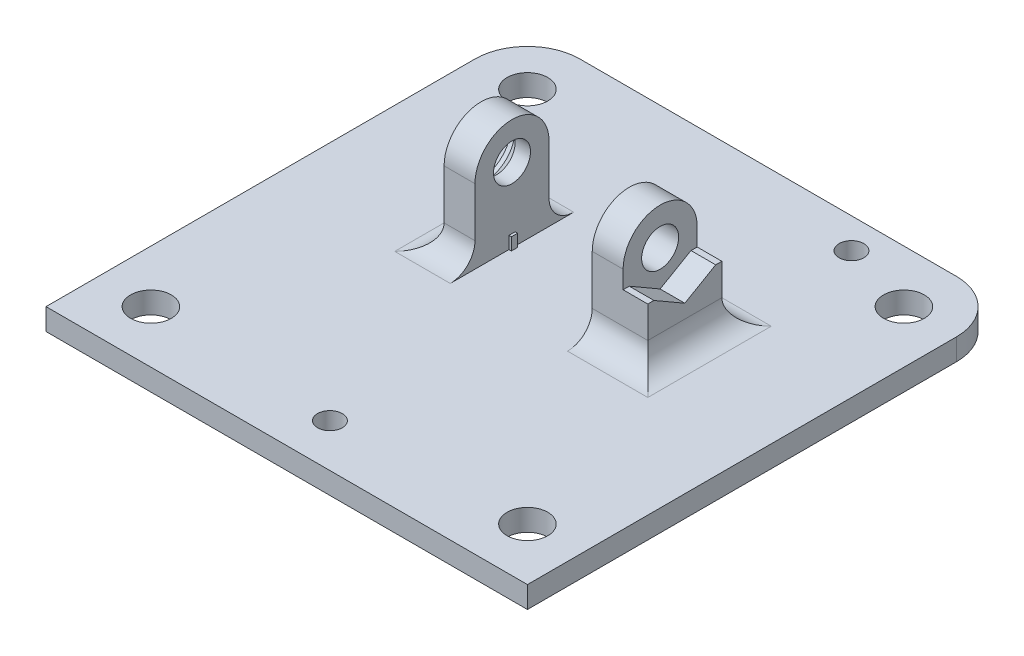
SolidWorks part; units mm, degrees
ref_plane "Front Plane" through (0, 0, 0) normal (0, 0, 1) x (1, 0, 0)
ref_plane "Top Plane" through (0, 0, 0) normal (0, 1, 0) x (1, 0, 0)
ref_plane "Right Plane" through (0, 0, 0) normal (1, 0, 0) x (0, 0, -1)
sketch "Sketch1" plane through (0, 0, 0) normal (0, 1, 0) x (1, 0, 0)
  line L0 (-19.5, 35.2) -> (-19.5, -19.5) construction
  line L1 (-19.5, 19.5) -> (19.5, 19.5)
  line L2 (-19.5, 19.5) -> (-19.5, -19.5)
  line L3 (-19.5, -19.5) -> (19.5, -19.5)
  line L4 (19.5, 19.5) -> (19.5, -19.5)
  line L5 (-19.5, 19.5) -> (19.5, -19.5) construction
  line L6 (-19.5, -19.5) -> (19.5, 19.5) construction
  line L7 (-19.5, -19.5) -> (19.5, -19.5) construction
  line L8 (0, -19.5) -> (0, 19.5) construction
  circle A0 centre (-15.25, -15.25) radius 1.65 construction
  circle A1 centre (15.25, -15.25) radius 1.65 construction
  circle A2 centre (9.2, 17.05) radius 1 construction
  circle A3 centre (15.25, 15.25) radius 1.65 construction
  circle A4 centre (-15.25, 15.25) radius 1.65 construction
  circle A5 centre (-15.25, -15.25) radius 1.65
  circle A6 centre (15.25, -15.25) radius 1.65
  circle A7 centre (9.2, 17.05) radius 1
  circle A8 centre (15.25, 15.25) radius 1.65
  circle A9 centre (-15.25, 15.25) radius 1.65
  circle A10 centre (-15.25, 15.25) radius 4.25
  circle A11 centre (15.25, 15.25) radius 4.25
  circle A12 centre (-15.25, -15.25) radius 4.25
  circle A13 centre (15.25, -15.25) radius 4.25
  circle A14 centre (0, -16) radius 1
  point P0 (0, 0)
  dimension "D1" = 2
  dimension "D2" = 3.5
extrude "Shape" add sketch "Sketch1" along normal blind 1.75 contours A13 L4 A11 L1 A10 L2 A12 L3 A7 | A10 A9 | A11 A8 | A13 A6 | A12 A5 | A12 L2 L3 | A13 L3 L4 region at (-0.0227, 0, 0.0026) region at (-12.3298, 0, -18.1702) region at (18.1702, 0, -18.1702) region at (-18.5507, 0, 18.5507) region at (-15.25, 0, 11.1202) region at (18.1702, 0, 18.1702) region at (18.5507, 0, 18.5507)
sketch "Sketch3" plane through (0, 1.75, 0) normal (0, 1, 0) x (1, 0, 0)
  line L0 (0, 19.5) -> (0, -19.5) construction
  line L1 (-15.25, 19.5) -> (15.25, 19.5) construction
  line L2 (-19.5, -19.5) -> (19.5, -19.5) construction
  line L3 (-19.5, 3.5) -> (19.5, 3.5) construction
  line L4 (-19.5, 15.25) -> (-19.5, -19.5) construction
  line L5 (19.5, 15.25) -> (19.5, -19.5) construction
  line L6 (4.75, 6.5) -> (7.25, 6.5)
  line L7 (-4.75, 6.5) -> (-7.25, 6.5)
  line L8 (-4.75, 6.5) -> (-4.75, 0.5)
  line L9 (-4.75, 0.5) -> (-7.25, 0.5)
  line L10 (-7.25, 6.5) -> (-7.25, 0.5)
  line L11 (-4.75, 6.5) -> (-7.25, 0.5) construction
  line L12 (-4.75, 0.5) -> (-7.25, 6.5) construction
  line L13 (4.75, 6.5) -> (4.75, 0.5)
  line L14 (4.75, 0.5) -> (7.25, 0.5)
  line L15 (7.25, 6.5) -> (7.25, 0.5)
  line L17 (7.25, 6.5) -> (9.25, 6.5)
  line L18 (7.25, 6.5) -> (7.25, 0.5)
  line L19 (7.25, 0.5) -> (9.25, 0.5)
  line L20 (9.25, 6.5) -> (9.25, 0.5)
  point P12 (-6, 3.5)
  dimension "D1" = 16
  dimension "D2" = 9.5
  dimension "D3" = 2.5
  dimension "D4" = 6
  dimension "D5" = 4.5
extrude "Supports" add sketch "Sketch3" along normal blind 9 contours L7 L10 L9 L8 | L15 L6 L13 L14 | L20 L17 L15 L19 region at (6, 1.75, -3.5) region at (8.25, 1.75, -3.5) region at (-6, 1.75, -3.5)
sketch "Sketch4" plane through (-7.25, 0, 0) normal (-1, 0, 0) x (0, 0, 1)
  line L0 (-3.5, 10.75) -> (-3.5, 1.75) construction
  line L2 (-6.5, 1.75) -> (-0.5, 1.75) construction
  line L3 (-0.5, 10.75) -> (-0.5, 1.75) construction
  line L4 (-6.5, 10.75) -> (-0.5, 10.75) construction
  circle A0 centre (-3.5, 7.75) radius 3
  circle A1 centre (-3.5, 7.75) radius 1.5
  line M2 (-0.5, 1.75) -> (-0.5, 10.75)
  line M4 (-6.5, 10.75) -> (-6.5, 1.75)
  line M11 (-0.5, 10.75) -> (-6.5, 10.75)
  dimension "D1" = 3
extrude "Support cuts" cut sketch "Sketch4" against normal up to surface (16.5 mm away) contours A1 L0 | L0 A1 | A0 M11 M4 | A0 M2 M11 region at (-7.25, 10.0799, -1.1701) region at (-7.25, 10.0799, -5.8299) region at (-7.25, 7.75, -2.8634) region at (-7.25, 7.75, -4.1366) up to face at (9.25, 6.25, -3.5)
fillet "Fillet1" radius 2 6 edges at (-6, 1.75, -6.5) (7, 1.75, -6.5) (7, 1.75, -0.5) (-6, 1.75, -0.5) (-7.25, 1.75, -3.5) (9.25, 1.75, -3.5)
sketch "Sketch5" plane through (9.25, 0, 0) normal (1, 0, 0) x (0, 0, -1)
  line L0 (1, 6.3066) -> (0.5, 6.3066)
  line L1 (3.5, 4.8632) -> (6, 6.3066)
  line L2 (6, 6.3066) -> (6, 9.1934)
  line L3 (6, 9.1934) -> (3.5, 10.6368)
  line L4 (3.5, 10.6368) -> (1, 9.1934)
  line L5 (1, 9.1934) -> (1, 6.3066)
  line L6 (1, 6.3066) -> (3.5, 4.8632)
  line L7 (6, 6.3066) -> (6.5, 6.3066)
  line L9 (0.5, 7.75) -> (0.5, 3.75)
  line L10 (0.5, 3.75) -> (6.5, 3.75)
  line L11 (6.5, 3.75) -> (6.5, 7.75)
  line L12 (0.5, 7.75) -> (0.5, 3.75)
  line L13 (0.5, 3.75) -> (6.5, 3.75)
  line L14 (6.5, 3.75) -> (6.5, 7.75)
  circle A0 centre (3.5, 7.75) radius 2.5 construction
  circle A1 centre (3.5, 7.75) radius 1.5 construction
  arc A2 (6.5, 7.75) -> (0.5, 7.75) centre (3.5, 7.75) ccw
  arc A3 (6.5, 7.75) -> (0.5, 7.75) centre (3.5, 7.75) ccw
  circle M3 centre (3.5, 7.75) radius 1.5
  line M4 (0.5, 7.75) -> (0.5, 3.75)
  line M6 (6.5, 3.75) -> (6.5, 7.75)
  arc M7 (6.5, 7.75) -> (0.5, 7.75) centre (3.5, 7.75) ccw
  dimension "D1" = 5
  dimension "D2" = 0
extrude "Nut holder" cut sketch "Sketch5" against normal blind 2 contours L5 L6 L1 L2 L3 L4 M3 | L2 L7 L0 L5 L4 L3 M6 M7 M4 region at (9.25, 6.3813, -0.75) region at (9.25, 7.75, -1.0764)
sketch "Sketch6" plane through (-7.25, 0, 0) normal (-1, 0, 0) x (0, 0, 1)
  circle A0 centre (-3.5, 7.75) radius 2.4
  dimension "D1" = 4.8
extrude "Screw cut" cut sketch "Sketch6" against normal blind 0.35
chamfer "Scew chamfer" distance 0.9 angle 45 1 edges at (-6.9, 7.75, -2)
sketch "Sketch7" plane through (4.75, 0, 0) normal (-1, 0, 0) x (0, 0, 1)
  line L0 (-3.5, 1.75) -> (-3.5, 10.75) construction
  line L1 (-8.5, 1.75) -> (1.5, 1.75) construction
  line L3 (-3.25, 2.75) -> (-3.75, 2.75)
  line L4 (-3.25, 2.75) -> (-3.25, 1.75)
  line L5 (-3.25, 1.75) -> (-3.75, 1.75)
  line L6 (-3.75, 2.75) -> (-3.75, 1.75)
  line L7 (-3.25, 2.75) -> (-3.75, 1.75) construction
  line L8 (-3.25, 1.75) -> (-3.75, 2.75) construction
  arc A0 (-0.5, 7.75) -> (-6.5, 7.75) centre (-3.5, 7.75) ccw construction
  point P7 (-3.5, 2.25)
  dimension "D1" = 0.5
  dimension "D2" = 1
extrude "Angle fix 1" add sketch "Sketch7" along normal blind 0.2
sketch "Sketch8" plane through (-4.75, 0, 0) normal (1, 0, 0) x (0, 0, -1)
  line L4 (3.75, 1.75) -> (3.75, 2.75)
  line L5 (3.25, 1.75) -> (3.75, 1.75)
  line L6 (3.25, 2.75) -> (3.25, 1.75)
  line L7 (3.75, 2.75) -> (3.25, 2.75)
  line L8 (3.75, 1.75) -> (3.75, 2.75)
  line L9 (3.25, 1.75) -> (3.75, 1.75)
  line L10 (3.25, 2.75) -> (3.25, 1.75)
  line L11 (3.75, 2.75) -> (3.25, 2.75)
  dimension "D1" = 0
extrude "Angle fix 2" add sketch "Sketch8" along normal blind 0.2
